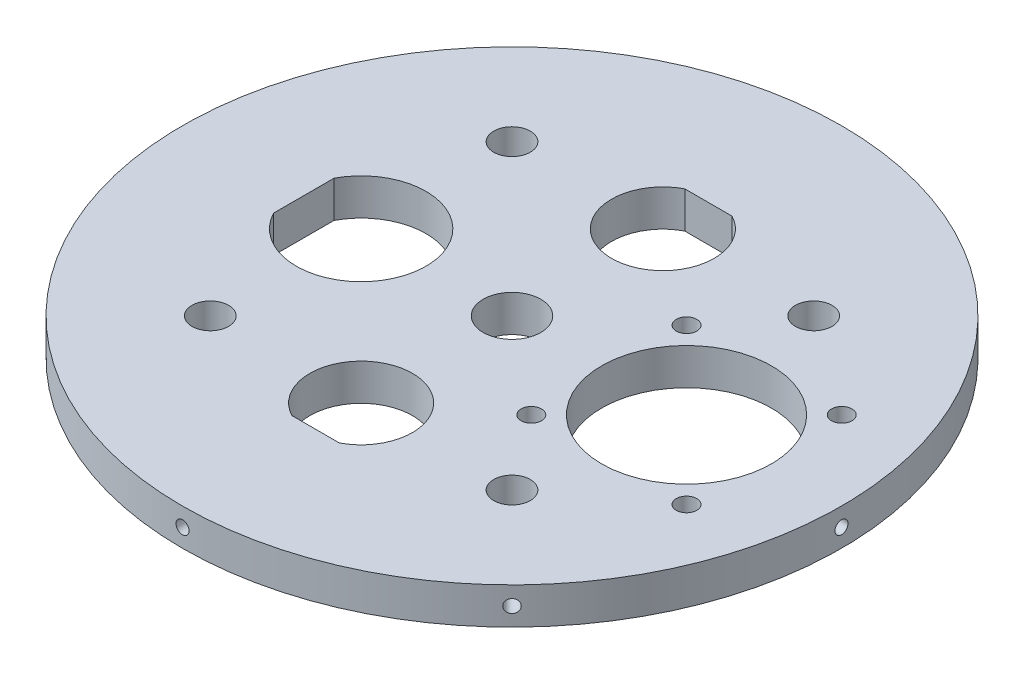
SolidWorks part; units mm, degrees
ref_plane "Front Plane" through (0, 0, 0) normal (0, 0, 1) x (1, 0, 0)
ref_plane "Top Plane" through (0, 0, 0) normal (0, 1, 0) x (1, 0, 0)
ref_plane "Right Plane" through (0, 0, 0) normal (1, 0, 0) x (0, 0, -1)
sketch "Sketch2" plane through (0, 0, 0) normal (0, 1, 0) x (1, 0, 0)
  circle A0 centre (0, 0) radius 57.15
  dimension "D1" = 114.3
extrude "Boss-Extrude1" add sketch "Sketch2" along normal blind 6.35 contours A0
sketch "Sketch6" plane through (0, 6.35, 0) normal (0, 1, 0) x (1, 0, 0)
  circle A0 centre (-26.1629, -26.1629) radius 3.175
  circle A1 centre (26.1629, -26.1629) radius 3.175
  circle A2 centre (-26.1629, 26.1631) radius 3.175
  circle A3 centre (26.1629, 26.1631) radius 3.175
  dimension "D1" = 6.35
  dimension "D2" = 74
  dimension "D3" = 26.1629
  dimension "D4" = 26.1629
  dimension "D5" = 26.1629
extrude "Cut-Extrude1" cut sketch "Sketch6" against normal up to next
sketch "Sketch7" plane through (0, 6.35, 0) normal (0, 1, 0) x (1, 0, 0)
  circle A0 centre (30, 0.2699) radius 14.732
  circle A3 centre (16.54, -13.1941) radius 1.778
  circle A4 centre (16.54, 13.7299) radius 1.778
  circle A5 centre (43.46, 13.7299) radius 1.778
  circle A6 centre (43.46, -13.1941) radius 1.778
  dimension "D1" = 29.464
  dimension "D2" = 3.556
  dimension "D3" = 3.556
  dimension "D4" = 3.556
  dimension "D5" = 3.556
  dimension "D6" = 13.46
  dimension "D7" = 13.46
  dimension "D8" = 13.46
  dimension "D9" = 13.464
  dimension "D10" = 30
extrude "Cut-Extrude2" cut sketch "Sketch7" against normal through all
sketch "Sketch8" plane through (0, 6.35, 0) normal (0, 1, 0) x (1, 0, 0)
  line L0 (4.0988, 34.0631) -> (-4.0988, 34.0631)
  line L1 (4.0988, -34.0629) -> (-4.0988, -34.0629)
  line L2 (-36.1129, 5.2498) -> (-36.1129, -5.2498)
  arc A0 (4.0988, -34.0629) -> (-4.0988, -34.0629) centre (0, -26.1629) ccw
  arc A1 (-4.0988, 34.0631) -> (4.0988, 34.0631) centre (0, 26.1631) ccw
  circle A2 centre (0, 0) radius 5
  arc A3 (-36.1129, -5.2498) -> (-36.1129, 5.2498) centre (-26.1629, 0) ccw
  circle A4 centre (26.1629, -26.1629) radius 3.175 construction
  circle A5 centre (26.1629, 26.1631) radius 3.175 construction
  circle A6 centre (-26.1629, -26.1629) radius 3.175 construction
  dimension "D1" = 17.8
  dimension "D2" = 17.8
  dimension "D3" = 10
  dimension "D4" = 22.5
  dimension "D5" = 7.9
  dimension "D6" = 0
  dimension "D7" = 7.9
  dimension "D8" = 0
  dimension "D9" = 9.95
  dimension "D10" = 0
extrude "Cut-Extrude3" cut sketch "Sketch8" against normal through all
sketch "Sketch10" plane through (0, 6.35, 0) normal (0, 1, 0) x (1, 0, 0)
  circle A0 centre (-26.1629, 26.1631) radius 7.9375
  circle A1 centre (26.1631, 26.1629) radius 7.9375
  circle A2 centre (26.1629, -26.1631) radius 7.9375
  circle A3 centre (-26.1631, -26.1629) radius 7.9375
  point P11 (0, 0)
  dimension "D1" = 4
sketch "Sketch11" plane through (0, 6.35, 0) normal (0, 1, 0) x (1, 0, 0)
  circle A0 centre (0, 0) radius 10
ref_plane "Plane1" through (0, 0, -57.15) normal (0, 0, -1) x (-1, 0, 0)
sketch "Sketch12" plane through (0, 0, -57.15) normal (0, 0, -1) x (-1, 0, 0)
  line L0 (57.15, 0) -> (57.15, 6.35) construction
  point P0 (0, 3.175)
  point P1 (57.15, 3.175)
hole_wizard "#4-40 Tapped Hole2" positions "3DSketch7" profile "Sketch16" tap size "#4-40" standard "ANSI Inch"
sketch3d "3DSketch7"
  point P0 (0, 3.175, -57.15)
sketch "Sketch16" plane through (0, 3.175, -57.15) normal (1, 0, 0) x (0, 1, 0)
  line L0 (0, 0) -> (0, 10.6792)
  line L1 (0, 10.6792) -> (1.1303, 10)
  line L2 (1.1303, 10) -> (1.1303, 0)
  line L5 (1.1303, 0) -> (0, 0)
  line L10 (0, 10.6792) -> (-1.1303, 10) construction
  line L11 (0, -6.35) -> (0, 107.95) construction
  dimension "Tap Drill Dia." = 2.2606
  dimension "Tap Drill Depth" = 10
  dimension "Drill Angle" = 118
cosmetic thread "Hole Thread2" parameters "D1"=5.69, "D2"=2.8448
pattern_circular "CirPattern1" count 8 over 360 about axis through (0, 0, 0) along (0, 1, 0) of "#4-40 Tapped Hole2"
cosmetic thread "Hole Thread3" parameters "D1"=5.69, "D2"=2.8448
cosmetic thread "Hole Thread4" parameters "D1"=5.69, "D2"=2.8448
cosmetic thread "Hole Thread5" parameters "D1"=5.69, "D2"=2.8448
cosmetic thread "Hole Thread6" parameters "D1"=5.69, "D2"=2.8448
cosmetic thread "Hole Thread7" parameters "D1"=5.69, "D2"=2.8448
cosmetic thread "Hole Thread8" parameters "D1"=5.69, "D2"=2.8448
cosmetic thread "Hole Thread9" parameters "D1"=5.69, "D2"=2.8448
equation "\"width\"=26.1629"
equation "\"D4@Sketch6\"=\"width\""
equation "\"D3@Sketch6\"=\"width\""
equation "\"D5@Sketch6\"=\"width\""
